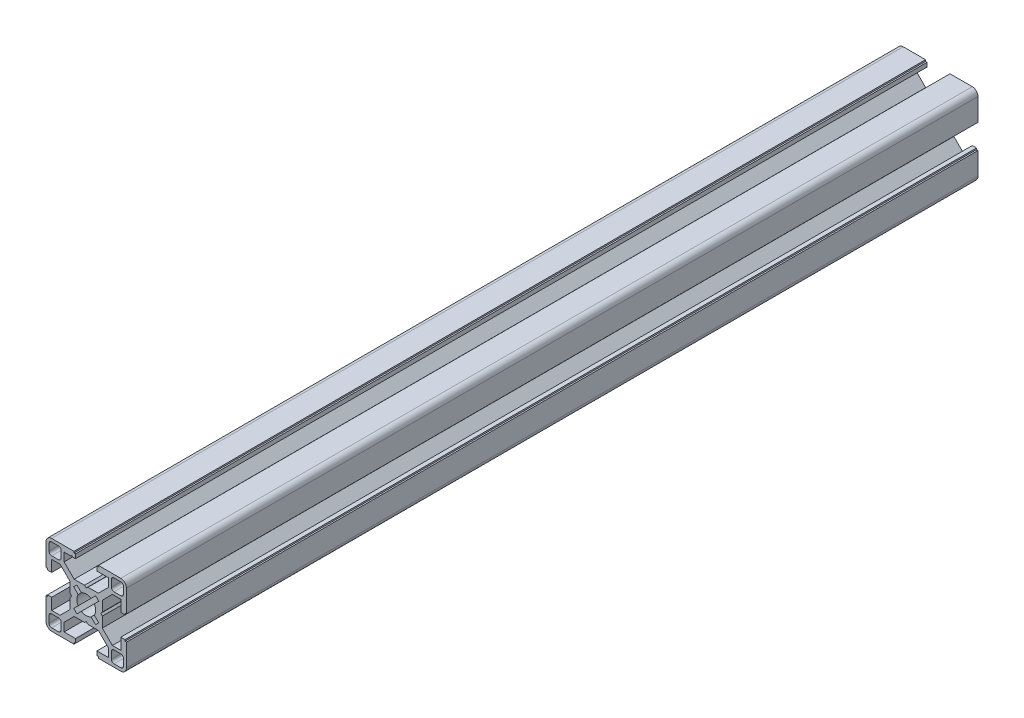
SolidWorks part; units mm, degrees
material "6061-T6 (SS)"
ref_plane "Front Plane" through (0, 0, 0) normal (0, 0, 1) x (1, 0, 0)
ref_plane "Top Plane" through (0, 0, 0) normal (0, 1, 0) x (1, 0, 0)
ref_plane "Right Plane" through (0, 0, 0) normal (1, 0, 0) x (0, 0, -1)
sketch "Sketch2" plane through (0, 0, 0) normal (0, 0, 1) x (1, 0, 0)
  line L0 (0, 15) -> (0, -15) construction
  line L1 (-15, 0) -> (15, 0) construction
  line L2 (4, -15) -> (15, -15)
  line L3 (15, -15) -> (15, -4)
  line L4 (4, -15) -> (4, -12.885)
  line L6 (8.25, -9.7455) -> (4.5045, -6)
  line L7 (0, 0) -> (15, -15) construction
  line L8 (15, -4) -> (12.885, -4)
  line L11 (4.55, -15) -> (4.55, -14.45) construction
  line L12 (4, -12.885) -> (8.25, -12.885)
  line L13 (8.25, -12.885) -> (8.25, -9.7455)
  line L14 (4.55, -14.45) -> (4, -14.45) construction
  line L15 (14.45, -4) -> (14.45, -4.55) construction
  line L16 (14.45, -4.55) -> (15, -4.55) construction
  line L17 (12.885, -4) -> (12.885, -8.25)
  line L18 (12.885, -8.25) -> (9.7455, -8.25)
  line L19 (9.7455, -8.25) -> (6, -4.5045)
  line L20 (7.8728, -6.3772) -> (6.3772, -7.8728) construction
  line L21 (11.625, -13.875) -> (11.625, -15) construction
  line L22 (9.375, -13.875) -> (13.875, -13.875)
  line L23 (9.375, -13.875) -> (9.375, -9.375)
  line L24 (9.375, -9.375) -> (13.875, -9.375)
  line L25 (13.875, -13.875) -> (13.875, -9.375)
  line L26 (11.625, -9.375) -> (11.625, -13.875) construction
  line L27 (9.375, -11.625) -> (13.875, -11.625) construction
  line L28 (13.875, -11.625) -> (15, -11.625) construction
  line L29 (8.25, -12.885) -> (9.375, -12.885) construction
  line L30 (4.5045, -6) -> (0.6555, -6)
  line L31 (0.6555, -6) -> (0, -5.45)
  line L32 (0, -6) -> (0, -5.45) construction
  circle A0 centre (0, 0) radius 3.5
  arc A2 (9.375, -12.885) -> (10.365, -13.875) centre (10.365, -12.885) ccw construction
  point P8 (0, -6)
  point P15 (4.55, -15)
  point P16 (7.125, -7.125)
  point P33 (11.625, -11.625)
  dimension "Center Hole Diameter" = 7
  dimension "Rail Height" = 30
  dimension "Rail Width" = 30
  dimension "T-Slot Width" = 8
  dimension "Slot Depth" = 9
  dimension "Slot Inner Width" = 16.5
  dimension "Step Width" = 9.1
  dimension "D1" = 1.125
  dimension "D2" = 2.115
  dimension "D3" = 50
sketch "Sketch3" plane through (0, 0, 0) normal (1, 0, 0) x (0, 0, -1)
  line L0 (-76.2, -15) -> (76.2, -15) construction
  line L1 (-50.8, 0) -> (50.8, 0) construction
  dimension "D1" = 25.4
  dimension "Length" = 152.4
sketch "Sketch4" plane through (0, 0, 0) normal (0, 0, 1) x (1, 0, 0)
  line L22 (0, -5.45) -> (0.6555, -6)
  line L23 (0.6555, -6) -> (4.5045, -6)
  line L24 (4.5045, -6) -> (8.25, -9.7455)
  line L25 (8.25, -9.7455) -> (8.25, -12.885)
  line L26 (8.25, -12.885) -> (4, -12.885)
  line L27 (4, -12.885) -> (4, -14.45)
  line L28 (4, -14.45) -> (4.55, -14.45)
  line L29 (4.55, -14.45) -> (4.55, -15)
  line L30 (4.55, -15) -> (12.885, -15)
  line L31 (4, -15) -> (15, -15) construction
  line L32 (15, -15) -> (15, -4) construction
  line L33 (15, -12.885) -> (15, -4.55)
  line L34 (15, -4.55) -> (14.45, -4.55)
  line L35 (14.45, -4.55) -> (14.45, -4)
  line L36 (14.45, -4) -> (12.885, -4)
  line L37 (12.885, -4) -> (12.885, -8.25)
  line L38 (12.885, -8.25) -> (9.7455, -8.25)
  line L39 (9.7455, -8.25) -> (6, -4.5045)
  line L40 (6, -4.5045) -> (6, -0.6555)
  line L41 (6, -0.6555) -> (5.45, 0)
  line L42 (-15, 0) -> (15, 0) construction
  line L43 (0, -5.45) -> (0, -3.5)
  line L44 (0, 15) -> (0, -15) construction
  line L45 (3.5, 0) -> (5.45, 0)
  line L46 (1.8108, -2.9952) -> (3.4913, -4.6757)
  line L47 (3.4913, -4.6757) -> (4.6757, -3.4913)
  line L48 (4.6757, -3.4913) -> (2.9952, -1.8108)
  line L49 (0, 0) -> (15, -15) construction
  line L50 (9.375, -13.875) -> (13.875, -13.875) construction
  line L51 (13.875, -13.875) -> (13.875, -9.375) construction
  line L52 (9.375, -13.875) -> (9.375, -9.375) construction
  line L53 (9.375, -9.375) -> (13.875, -9.375) construction
  line L54 (9.375, -10.365) -> (9.375, -12.885)
  line L55 (10.365, -13.875) -> (12.885, -13.875)
  line L56 (13.875, -12.885) -> (13.875, -10.365)
  line L57 (10.365, -9.375) -> (12.885, -9.375)
  arc A12 (12.885, -15) -> (15, -12.885) centre (12.885, -12.885) ccw
  circle A13 centre (0, 0) radius 3.5 construction
  arc A14 (0, -3.5) -> (1.8108, -2.9952) centre (0, 0) ccw
  arc A15 (3.5, 0) -> (2.9952, -1.8108) centre (0, 0) cw
  circle A16 centre (0, 0) radius 5.775 construction
  arc A17 (9.375, -12.885) -> (10.365, -13.875) centre (10.365, -12.885) ccw
  arc A18 (9.375, -12.885) -> (10.365, -13.875) centre (10.365, -12.885) ccw construction
  arc A19 (12.885, -13.875) -> (13.875, -12.885) centre (12.885, -12.885) ccw
  arc A20 (9.375, -10.365) -> (10.365, -9.375) centre (10.365, -10.365) cw
  arc A21 (12.885, -9.375) -> (13.875, -10.365) centre (12.885, -10.365) cw
  point P40 (4.0835, -4.0835)
  dimension "D1" = 11.55
  dimension "D2" = 0.22
extrude "Boss-Extrude1" add sketch "Sketch4" along normal blind 317.5
mirror "Mirror1" about plane through (0, 0, 0) normal (1, 0, 0) of bodies 134
mirror "Mirror2" about plane through (0, 0, 0) normal (0, 1, 0) of bodies 135
sketch "Sketch5" plane through (0, 0, 317.5) normal (0, 0, 1) x (1, 0, 0)
  line L0 (-5.675, 12.885) -> (-5.4, 13.16)
  line L1 (-8.25, 12.885) -> (-4, 12.885) construction
  line L2 (-5.4, 13.16) -> (-5.125, 12.885)
  line L3 (0, 15) -> (0, -15) construction
  line L4 (-5.675, 12.885) -> (-5.125, 12.885)
  dimension "D1" = 0.275
  dimension "D2" = 5.4
extrude "Cut-Extrude1" cut sketch "Sketch5" against normal through all both and the other way through all
equation "\"D1@Sketch2\"= \"Slot Depth@Sketch2\" * 0.125"
equation "\"D2@Sketch2\"=\"Slot Depth@Sketch2\"*0.235"
equation "\"D1@Sketch4\"=\"Center Hole Diameter@Sketch2\"*1.65"
equation "\"D2@Sketch4\"=(\"Step Width@Sketch2\"-\"T-Slot Width@Sketch2\")*0.2"
equation "\"D1@Sketch5\"=(\"Step Width@Sketch2\"-\"T-Slot Width@Sketch2\")*0.5*0.5"
equation "\"D2@Sketch5\"=\"T-Slot Width@Sketch2\"*1.35*0.5"
equation "\"altitude_horizontal_rail_length\"=10in"
equation "\"altitude_vertictal_rail_length\"=12in"
equation "\"table_length\"=72in"
equation "\"table_width\"=25in"
equation "\"table_thickness\"=1.75in"
equation "\"azimuth_horizontal_rail_length\"=(\"altitude_horizontal_rail_length\"+6in-0.29in)"
equation "\"azimuth_vertictal_rail_length_short\"=(\"altitude_vertictal_rail_length\"-5in)"
equation "\"azimuth_vertictal_rail_length_long\"=(\"azimuth_vertictal_rail_length_short\"+4in)"
equation "\"azimuth_mounting_hole_distance\"=9in"
equation "\"table_frame_vertical_length\"=12.5in"
equation "\"D1@Boss-Extrude1\"=\"table_frame_vertical_length\""
